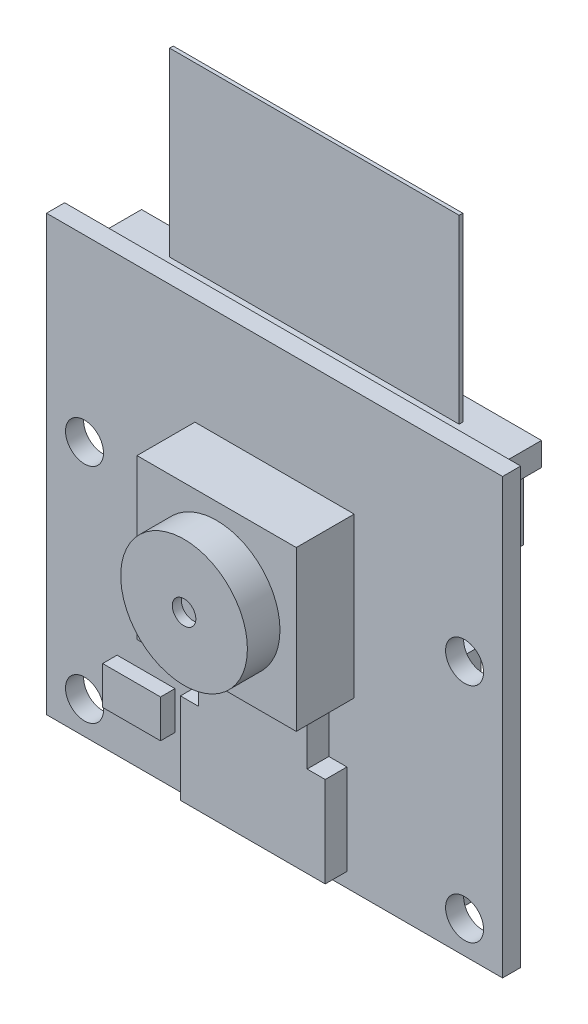
SolidWorks part; units mm, degrees
ref_plane "Přední rovina" through (0, 0, 0) normal (0, 0, 1) x (1, 0, 0)
ref_plane "Horní rovina" through (0, 0, 0) normal (0, 1, 0) x (1, 0, 0)
ref_plane "Pravá rovina" through (0, 0, 0) normal (1, 0, 0) x (0, 0, -1)
sketch "Skica1" plane through (0, 0, 0) normal (0, 0, 1) x (1, 0, 0)
  line L0 (0, -4.05) -> (0, 0) construction
  line L6 (-4.4, -2.7) -> (4.4, -2.7)
  line L7 (-21.3919, 19.9602) -> (21.3919, 19.9602)
  line L8 (-21.3919, 19.9602) -> (-21.3919, -19.9602)
  line L9 (-21.3919, -19.9602) -> (21.3919, -19.9602)
  line L10 (21.3919, 19.9602) -> (21.3919, -19.9602)
  line L11 (-21.3919, 19.9602) -> (21.3919, -19.9602) construction
  line L12 (-21.3919, -19.9602) -> (21.3919, 19.9602) construction
  line L13 (10.5, -10.2) -> (-10.5, -10.2) construction
  line L14 (10.5, -10.2) -> (10.5, 2.1) construction
  line L15 (10.5, 2.1) -> (-10.5, 2.1) construction
  line L16 (-10.5, -10.2) -> (-10.5, 2.1) construction
  line L17 (10.5, -10.2) -> (-10.5, 2.1) construction
  line L18 (10.5, 2.1) -> (-10.5, -10.2) construction
  line L19 (0, -4.05) -> (46.9713, -4.05) construction
  line L20 (-4.4, -2.7) -> (-4.4, 6.1)
  line L21 (12.6, -12) -> (-12.6, -12)
  line L22 (12.6, -12) -> (12.6, 12)
  line L23 (12.6, 12) -> (-12.6, 12)
  line L24 (-12.6, -12) -> (-12.6, 12)
  line L25 (12.6, -12) -> (-12.6, 12) construction
  line L26 (12.6, 12) -> (-12.6, -12) construction
  line L27 (-4.4, 6.1) -> (4.4, 6.1)
  line L28 (4.4, -2.7) -> (4.4, 6.1)
  line L29 (-4.4, -2.7) -> (4.4, 6.1) construction
  line L30 (-4.4, 6.1) -> (4.4, -2.7) construction
  circle A0 centre (-10.5, 2.1) radius 1.05
  circle A1 centre (10.5, 2.1) radius 1.05
  circle A2 centre (10.5, -10.2) radius 1.05
  circle A3 centre (-10.5, -10.2) radius 1.05
  circle A4 centre (0, 1.7) radius 3.5
  point P0 (41.1239, 15.3264)
  point P1 (0, 1.7)
  point P5 (0, 12)
  point P6 (0, 0)
  point P44 (0, 0)
  dimension "D5" = 2.1
  dimension "D6" = 0.75
  dimension "D8" = 7
  dimension "D1" = 25.2
  dimension "D2" = 24
  dimension "D3" = 12.3
  dimension "D4" = 21
  dimension "D7" = 8.8
  dimension "D9" = 5.9
extrude "Přidat vysunutím1" add sketch "Skica1" against normal blind 1 contours L24 L21 L22 L23 A1 A0 L28 L6 L20 L27 A2 A3 | L6 L28 L27 L20 A4 | A4 region at (-4.2755, 1.7, 0) region at (0, -11.652, 0) region at (0, 1.7, 0)
extrude "Přidat vysunutím2" add sketch "Skica1<3>" along normal blind 3.2 contours L6 L28 L27 L20 A4 region at (-4.2755, 1.7, 0)
sketch "Skica1<3>" plane through (0, 0, 0) normal (0, 0, 1) x (1, 0, 0) same geometry as "Skica1"
extrude "Přidat vysunutím3" add sketch "Skica1<4>" along normal blind 5 contours A4 region at (0, 1.7, 0)
sketch "Skica1<4>" plane through (0, 0, 0) normal (0, 0, 1) x (1, 0, 0) same geometry as "Skica1"
sketch "Skica2" plane through (0, 0, 0) normal (0, 0, 1) x (1, 0, 0)
  line L0 (-4.4, -2.7) -> (4.4, -2.7) construction
  line L1 (-4, -11.2) -> (4, -11.2)
  line L2 (-4, -11.2) -> (-4, -6.2)
  line L3 (-4, -6.2) -> (4, -6.2)
  line L4 (4, -11.2) -> (4, -6.2)
  line L5 (-4, -11.2) -> (4, -6.2) construction
  line L6 (-4, -6.2) -> (4, -11.2) construction
  line L7 (-3, -6.2) -> (3, -6.2)
  line L8 (-3, -6.2) -> (-3, -2.7)
  line L9 (-3, -2.7) -> (3, -2.7)
  line L10 (3, -6.2) -> (3, -2.7)
  line L11 (-3, -6.2) -> (3, -2.7) construction
  line L12 (-3, -2.7) -> (3, -6.2) construction
  line L13 (-4.4, -2.7) -> (4.4, -2.7) construction
  point P0 (0, -8.7)
  point P5 (0, -4.45)
  line M18 (4.4, -2.7) -> (-4.4, -2.7)
  dimension "D1" = 8
  dimension "D2" = 5
  dimension "D3" = 8.5
  dimension "D4" = 6
extrude "Přidat vysunutím4" add sketch "Skica2" along normal blind 1.2 contours L1 L4 L3 L2 | L3 L10 L8 M18 region at (0, -8.7, 0) region at (0, -4.45, 0)
sketch "Skica3" plane through (0, 0, -1) normal (0, 0, -1) x (-1, 0, 0)
  line L0 (-12.6, 12) -> (12.6, 12) construction
  line L1 (-10.05, 5.6) -> (10.05, 5.6)
  line L2 (-10.05, 5.6) -> (-10.05, 9.8)
  line L3 (-10.05, 9.8) -> (10.05, 9.8)
  line L4 (10.05, 5.6) -> (10.05, 9.8)
  line L5 (-10.05, 5.6) -> (10.05, 9.8) construction
  line L6 (-10.05, 9.8) -> (10.05, 5.6) construction
  line L7 (-11.05, 9.8) -> (11.05, 9.8)
  line L8 (-11.05, 9.8) -> (-11.05, 11.1)
  line L9 (-11.05, 11.1) -> (11.05, 11.1)
  line L10 (11.05, 9.8) -> (11.05, 11.1)
  line L11 (-11.05, 9.8) -> (11.05, 11.1) construction
  line L12 (-11.05, 11.1) -> (11.05, 9.8) construction
  point P0 (0, 7.7)
  point P5 (0, 10.45)
  dimension "D1" = 22.1
  dimension "D2" = 20.1
  dimension "D3" = 4.2
  dimension "D4" = 1.3
  dimension "D5" = 0.9
extrude "Přidat vysunutím5" add sketch "Skica3" along normal blind 2.7 contours L1 L4 L3 L2 | L7 L10 L9 L8 L3 region at (0, 7.7, -1) region at (0, 10.45, -1)
sketch "Skica4" plane through (0, 0, -1) normal (0, 0, -1) x (-1, 0, 0)
  line L0 (-12.6, -12) -> (12.6, -12) construction
  line L1 (8.8, -11) -> (-9.1, -11)
  line L2 (8.8, -11) -> (8.8, 1)
  line L3 (8.8, 1) -> (-9.1, 1)
  line L4 (-9.1, -11) -> (-9.1, 1)
  line L5 (8.8, -11) -> (-9.1, 1) construction
  line L6 (8.8, 1) -> (-9.1, -11) construction
  line L7 (12.6, -12) -> (12.6, 12) construction
  line L8 (-12.6, -12) -> (-12.6, 12) construction
  point P0 (-0.15, -5)
  dimension "D1" = 1
  dimension "D2" = 3.8
  dimension "D3" = 3.5
  dimension "D4" = 13
extrude "Přidat vysunutím6" add sketch "Skica4" along normal blind 1.3
sketch "Skica5" plane through (0, 0, 0) normal (0, 0, 1) x (1, 0, 0)
  line L0 (-12.6, -12) -> (-12.6, 12) construction
  line L1 (-8.7, -9.3) -> (-5.5, -9.3)
  line L2 (-8.7, -9.3) -> (-8.7, -7.2)
  line L3 (-8.7, -7.2) -> (-5.5, -7.2)
  line L4 (-5.5, -9.3) -> (-5.5, -7.2)
  line L5 (-8.7, -9.3) -> (-5.5, -7.2) construction
  line L6 (-8.7, -7.2) -> (-5.5, -9.3) construction
  line L7 (12.6, -12) -> (-12.6, -12) construction
  point P0 (-7.1, -8.25)
  dimension "D1" = 2.1
  dimension "D2" = 3.2
  dimension "D3" = 3.9
  dimension "D4" = 2.7
extrude "Přidat vysunutím7" add sketch "Skica5" along normal blind 0.8
sketch "Skica6" plane through (0, 0, 5) normal (0, 0, 1) x (1, 0, 0)
  circle A0 centre (0, 1.7) radius 0.65
  dimension "D1" = 1.3
extrude "Odebrat vysunutím1" cut sketch "Skica6" against normal blind 0.5
sketch "Skica7" plane through (0, 11.1, 0) normal (0, 1, 0) x (1, 0, 0)
  line L0 (11.05, 3.7) -> (-11.05, 3.7) construction
  line L1 (8, 2.4) -> (-8, 2.4)
  line L2 (8, 2.4) -> (8, 2.2)
  line L3 (8, 2.2) -> (-8, 2.2)
  line L4 (-8, 2.4) -> (-8, 2.2)
  line L5 (8, 2.4) -> (-8, 2.2) construction
  line L6 (8, 2.2) -> (-8, 2.4) construction
  point P0 (0, 2.3)
  dimension "D1" = 16
  dimension "D2" = 0.2
  dimension "D3" = 1.3
extrude "Přidat vysunutím9" add sketch "Skica7" along normal blind 10
ref_point "Ponto1"
ref_point "Ponto2"
ref_axis "Eixo1" through (10.5, 2.1, 0) along (-1, 0, 0)
